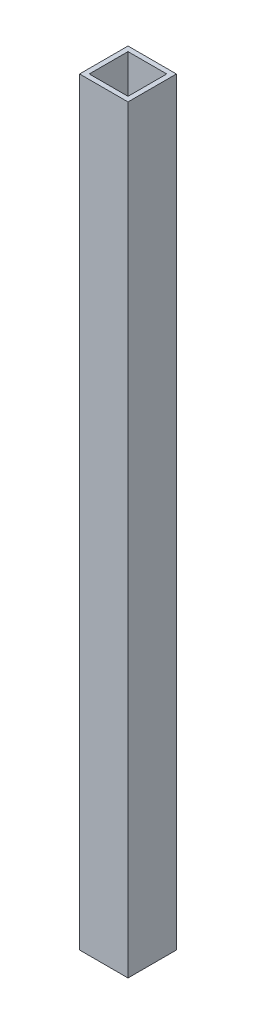
SolidWorks part; units mm, degrees
material "6061 Alloy"
ref_plane "Front Plane" through (0, 0, 0) normal (0, 0, 1) x (1, 0, 0)
ref_plane "Top Plane" through (0, 0, 0) normal (0, 1, 0) x (1, 0, 0)
ref_plane "Right Plane" through (0, 0, 0) normal (1, 0, 0) x (0, 0, -1)
sketch "Sketch1" plane through (0, 0, 0) normal (0, 1, 0) x (1, 0, 0)
  line L1 (0, 0) -> (15, 0)
  line L2 (0, 0) -> (0, 15)
  line L3 (0, 15) -> (15, 15)
  line L4 (15, 0) -> (15, 15)
  dimension "D1" = 15
extrude "Extrude-Thin1" add sketch "Sketch1" along normal blind 235 thin thin type one direction reverse wall 1.5
